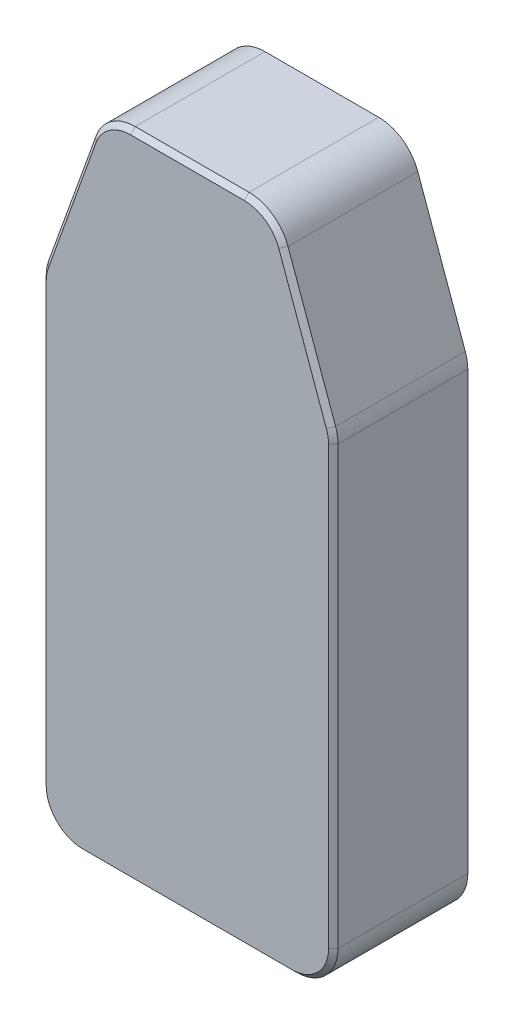
SolidWorks part; units mm, degrees
ref_plane "Front Plane" through (0, 0, 0) normal (0, 0, 1) x (1, 0, 0)
ref_plane "Top Plane" through (0, 0, 0) normal (0, 1, 0) x (1, 0, 0)
ref_plane "Right Plane" through (0, 0, 0) normal (1, 0, 0) x (0, 0, -1)
sketch "Sketch1" plane through (0, 0, 0) normal (0, 0, 1) x (1, 0, 0)
  line L36 (-30.2974, 123.4372) -> (-45.3256, 81.692)
  line L37 (-46.1, 77.2548) -> (-46.1, -60.7336)
  line L38 (-33, -73.8336) -> (33, -73.8336)
  line L39 (46.1, -60.7336) -> (46.1, 77.2548)
  line L40 (45.3256, 81.692) -> (30.2974, 123.4372)
  line L41 (17.9717, 132.1) -> (-17.9717, 132.1)
  line L42 (-27.4747, 122.4211) -> (-42.503, 80.6759)
  line L43 (-43.1, 77.2548) -> (-43.1, -60.7336)
  line L44 (-33, -70.8336) -> (33, -70.8336)
  line L45 (43.1, -60.7336) -> (43.1, 77.2548)
  line L46 (42.503, 80.6759) -> (27.4747, 122.4211)
  line L47 (17.9717, 129.1) -> (-17.9717, 129.1)
  line L48 (-27.4747, 122.4211) -> (-42.503, 80.6759)
  line L49 (-43.1, 77.2548) -> (-43.1, -60.7336)
  line L50 (-33, -70.8336) -> (33, -70.8336)
  line L51 (43.1, -60.7336) -> (43.1, 77.2548)
  line L52 (42.503, 80.6759) -> (27.4747, 122.4211)
  line L53 (17.9717, 129.1) -> (-17.9717, 129.1)
  arc A42 (-45.3256, 81.692) -> (-46.1, 77.2548) centre (-33, 77.2548) ccw
  arc A43 (-46.1, -60.7336) -> (-33, -73.8336) centre (-33, -60.7336) ccw
  arc A44 (33, -73.8336) -> (46.1, -60.7336) centre (33, -60.7336) ccw
  arc A45 (46.1, 77.2548) -> (45.3256, 81.692) centre (33, 77.2548) ccw
  arc A46 (30.2974, 123.4372) -> (17.9717, 132.1) centre (17.9717, 119) ccw
  arc A47 (-17.9717, 132.1) -> (-30.2974, 123.4372) centre (-17.9717, 119) ccw
  arc A48 (-42.503, 80.6759) -> (-43.1, 77.2548) centre (-33, 77.2548) ccw
  arc A49 (-43.1, -60.7336) -> (-33, -70.8336) centre (-33, -60.7336) ccw
  arc A50 (33, -70.8336) -> (43.1, -60.7336) centre (33, -60.7336) ccw
  arc A51 (43.1, 77.2548) -> (42.503, 80.6759) centre (33, 77.2548) ccw
  arc A52 (27.4747, 122.4211) -> (17.9717, 129.1) centre (17.9717, 119) ccw
  arc A53 (-17.9717, 129.1) -> (-27.4747, 122.4211) centre (-17.9717, 119) ccw
  arc A54 (-42.503, 80.6759) -> (-43.1, 77.2548) centre (-33, 77.2548) ccw
  arc A55 (-43.1, -60.7336) -> (-33, -70.8336) centre (-33, -60.7336) ccw
  arc A56 (33, -70.8336) -> (43.1, -60.7336) centre (33, -60.7336) ccw
  arc A57 (43.1, 77.2548) -> (42.503, 80.6759) centre (33, 77.2548) ccw
  arc A58 (27.4747, 122.4211) -> (17.9717, 129.1) centre (17.9717, 119) ccw
  arc A59 (-17.9717, 129.1) -> (-27.4747, 122.4211) centre (-17.9717, 119) ccw
  dimension "D1" = 0.1
  dimension "D2" = 3
extrude "Boss-Extrude1" add sketch "Sketch1" along normal blind 41
sketch "Sketch2" plane through (0, 0, 41) normal (0, 0, 1) x (1, 0, 0)
  line L6 (17.9717, 132.1) -> (-17.9717, 132.1)
  line L7 (-30.2974, 123.4372) -> (-45.3256, 81.692)
  line L8 (-46.1, 77.2548) -> (-46.1, -60.7336)
  line L9 (-33, -73.8336) -> (33, -73.8336)
  line L10 (46.1, -60.7336) -> (46.1, 77.2548)
  line L11 (45.3256, 81.692) -> (30.2974, 123.4372)
  line L12 (17.9717, 132.1) -> (-17.9717, 132.1)
  line L13 (-30.2974, 123.4372) -> (-45.3256, 81.692)
  line L14 (-46.1, 77.2548) -> (-46.1, -60.7336)
  line L15 (-33, -73.8336) -> (33, -73.8336)
  line L16 (46.1, -60.7336) -> (46.1, 77.2548)
  line L17 (45.3256, 81.692) -> (30.2974, 123.4372)
  arc A6 (-17.9717, 132.1) -> (-30.2974, 123.4372) centre (-17.9717, 119) ccw
  arc A7 (-45.3256, 81.692) -> (-46.1, 77.2548) centre (-33, 77.2548) ccw
  arc A8 (-46.1, -60.7336) -> (-33, -73.8336) centre (-33, -60.7336) ccw
  arc A9 (33, -73.8336) -> (46.1, -60.7336) centre (33, -60.7336) ccw
  arc A10 (46.1, 77.2548) -> (45.3256, 81.692) centre (33, 77.2548) ccw
  arc A11 (30.2974, 123.4372) -> (17.9717, 132.1) centre (17.9717, 119) ccw
  arc A12 (-17.9717, 132.1) -> (-30.2974, 123.4372) centre (-17.9717, 119) ccw
  arc A13 (-45.3256, 81.692) -> (-46.1, 77.2548) centre (-33, 77.2548) ccw
  arc A14 (-46.1, -60.7336) -> (-33, -73.8336) centre (-33, -60.7336) ccw
  arc A15 (33, -73.8336) -> (46.1, -60.7336) centre (33, -60.7336) ccw
  arc A16 (46.1, 77.2548) -> (45.3256, 81.692) centre (33, 77.2548) ccw
  arc A17 (30.2974, 123.4372) -> (17.9717, 132.1) centre (17.9717, 119) ccw
  dimension "D1" = 0
extrude "Boss-Extrude2" add sketch "Sketch2" along normal blind 1.5
chamfer "Chamfer1" distance 1.5 angle 45 24 edges at (37.8115, 102.5646, 42.5) (45.905, 79.507, 42.5) (46.1, 8.2606, 42.5) (42.2631, -69.9967, 42.5) (0, -73.8336, 42.5) (-42.2631, -69.9967, 42.5) (-46.1, 8.2606, 42.5) (-45.905, 79.507, 42.5) (-37.8115, 102.5646, 42.5) (-25.5044, 129.7177, 42.5) (0, 132.1, 42.5) (25.5044, 129.7177, 42.5) (0, -70.8336, 0) (40.1418, -67.8754, 0) (-40.1418, -67.8754, 0) (43.1, 8.2606, 0) (-43.1, 8.2606, 0) (42.9496, 78.9912, 0) (-42.9496, 78.9912, 0) (34.9888, 101.5485, 0) (-34.9888, 101.5485, 0) (23.7794, 127.2633, 0) (-23.7794, 127.2633, 0) (0, 129.1, 0)
